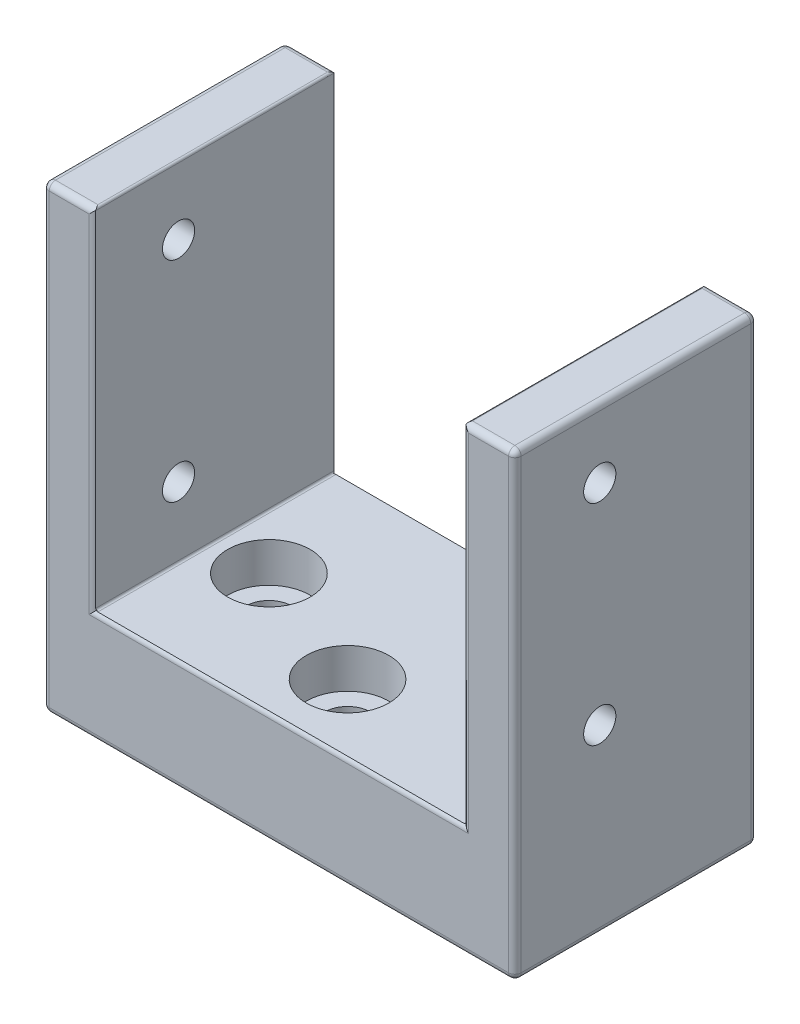
SolidWorks part; units mm, degrees
material "PLA"
ref_plane "Front Plane" through (0, 0, 0) normal (0, 0, 1) x (1, 0, 0)
ref_plane "Top Plane" through (0, 0, 0) normal (0, 1, 0) x (1, 0, 0)
ref_plane "Right Plane" through (0, 0, 0) normal (1, 0, 0) x (0, 0, -1)
sketch "Sketch1" plane through (0, 0, 0) normal (0, 1, 0) x (1, 0, 0)
  line L1 (-22.225, 14.6625) -> (22.225, 14.6625)
  line L2 (-22.225, 14.6625) -> (-22.225, -14.6625)
  line L3 (-22.225, -14.6625) -> (22.225, -14.6625)
  line L4 (22.225, 14.6625) -> (22.225, -14.6625)
  point P4 (0, -14.6625)
  point P6 (-22.225, 0)
  dimension "D1" = 29.325
  dimension "D2" = 44.45
extrude "Boss-Extrude1" add sketch "Sketch1" against normal blind 13.685
sketch "Sketch2" plane through (22.225, 0, 0) normal (1, 0, 0) x (0, 0, -1)
  line L0 (14.6625, -13.685) -> (14.6625, 0) construction
  line L1 (-14.6625, -13.685) -> (14.6625, -13.685)
  line L2 (-14.6625, -13.685) -> (-14.6625, 42)
  line L3 (-14.6625, 42) -> (14.6625, 42)
  line L4 (14.6625, -13.685) -> (14.6625, 42)
  point P5 (-4.3875, 33.7)
  point P6 (-4.3875, 8.3)
  dimension "D1" = 55.685
extrude "Boss-Extrude2" add sketch "Sketch2" along normal blind 6.35
hole_wizard "M3.5 Clearance Hole1" positions "Sketch5" profile "Sketch6" hole size "M3.5" standard "ANSI Metric" end condition through all
sketch "Sketch5" plane through (28.575, 0, 0) normal (1, 0, 0) x (0, 0, -1)
  line L1 (14.6625, 42) -> (-14.6625, 42) construction
  line L2 (-14.6625, 42) -> (-14.6625, -13.685) construction
  point P0 (-4.3875, 33.7)
  point P2 (-4.3875, 8.3)
  dimension "D1" = 10.275
  dimension "D2" = 8.3
  dimension "D3" = 25.4
sketch "Sketch6" plane through (28.575, 33.7, 4.3875) normal (0, 1, 0) x (0, 0, -1)
  line L0 (0, 0) -> (0, 50.8)
  line L1 (0, 50.8) -> (1.95, 50.8)
  line L2 (1.95, 50.8) -> (1.95, 0)
  line L5 (1.95, 0) -> (0, 0)
  line L11 (0, -6.35) -> (0, 107.95) construction
  dimension "Thru Hole Dia." = 3.9
  dimension "Thru Hole Depth" = 50.8
mirror "Mirror1" about plane through (0, 0, 0) normal (1, 0, 0) of "Boss-Extrude2", "M3.5 Clearance Hole1"
sketch "Sketch8" plane through (22.225, 0, 0) normal (-1, 0, 0) x (0, 0, 1)
  line L0 (-14.6625, 42) -> (14.6625, 42) construction
  line L1 (-14.6625, 0) -> (-1.9625, 0)
  line L2 (-14.6625, 0) -> (-14.6625, 42)
  line L3 (-14.6625, 42) -> (-1.9625, 42)
  line L4 (-1.9625, 0) -> (-1.9625, 42)
  dimension "D1" = 12.7
hole_wizard "CBORE for M5 SHCS1" positions "Sketch9" profile "Sketch10" counterbore size "M5" standard "ANSI Metric" end condition through all
sketch "Sketch9" plane through (0, 0, 0) normal (0, 1, 0) x (1, 0, 0)
  line L0 (-22.225, 14.6625) -> (-22.225, -14.6625) construction
  line L1 (0, -16.1288) -> (0, 16.1288) construction
  point P0 (15.875, 0)
  point P2 (-15.875, 0)
  point P8 (-22.225, 0)
  point P12 (0, -6.35)
  dimension "D1" = 15.875
  dimension "D2" = 15.875
  dimension "D3" = 6.35
sketch "Sketch10" plane through (15.875, 0, 0) normal (1, 0, 0) x (0, 0, 1)
  line L0 (0, 0) -> (0, 13.685)
  line L1 (0, 13.685) -> (2.75, 13.685)
  line L3 (2.75, 13.685) -> (2.75, 5)
  line L4 (2.75, 5) -> (5, 5)
  line L5 (5, 5) -> (5, 0)
  line L7 (5, 0) -> (0, 0)
  line L11 (0, -6.35) -> (0, 107.95) construction
  dimension "Thru Hole Dia." = 5.5
  dimension "Thru Hole Depth" = 13.685
  dimension "C'Bore Dia." = 10
  dimension "C'Bore Depth" = 5
fillet "Fillet1" radius 0.762 23 edges at (0, -13.685, -14.6625) (22.225, 21, 14.6625) (25.4, 42, 14.6625) (22.225, 21, -14.6625) (25.4, 42, -14.6625) (28.575, 14.1575, 14.6625) (28.575, -13.685, 0) (28.575, 14.1575, -14.6625) (28.575, 42, 0) (-22.225, 21, -14.6625) (-22.225, 21, 14.6625) (-28.575, 14.1575, 14.6625) (-28.575, 42, 0) (-25.4, 42, 14.6625) (-28.575, 14.1575, -14.6625) (-25.4, 42, -14.6625) (-28.575, -13.685, 0) (0, 0, -14.6625) (0, 0, 14.6625) (0, -13.685, 9.1) (-15.875, -13.685, 2.75) (15.875, -13.685, 2.75) (0, -13.685, 14.6625)
fillet "Fillet2" [suppressed] radius 0.762
sketch "Sketch11" plane through (0, 0, 0) normal (0, 1, 0) x (1, 0, 0)
  line L1 (-22.4282, 14.6625) -> (22.4282, 14.6625)
  line L2 (-22.4282, 14.6625) -> (-22.4282, -14.6625)
  line L3 (-22.4282, -14.6625) -> (22.4282, -14.6625)
  line L4 (22.4282, 14.6625) -> (22.4282, -14.6625)
  line L5 (22.225, 14.6625) -> (-22.225, 14.6625) construction
  line L6 (-22.225, -14.6625) -> (22.225, -14.6625) construction
  point P6 (0, 14.6625)
  dimension "D1" = 44.8564
extrude "Cut-Extrude1" cut sketch "Sketch11" along normal through all and the other way blind 0.2032
fillet "Fillet3" radius 0.254 4 edges at (-22.4282, 42, 0) (22.4282, 42, 0) (-22.4282, -0.2032, 0) (22.4282, -0.2032, 0)
